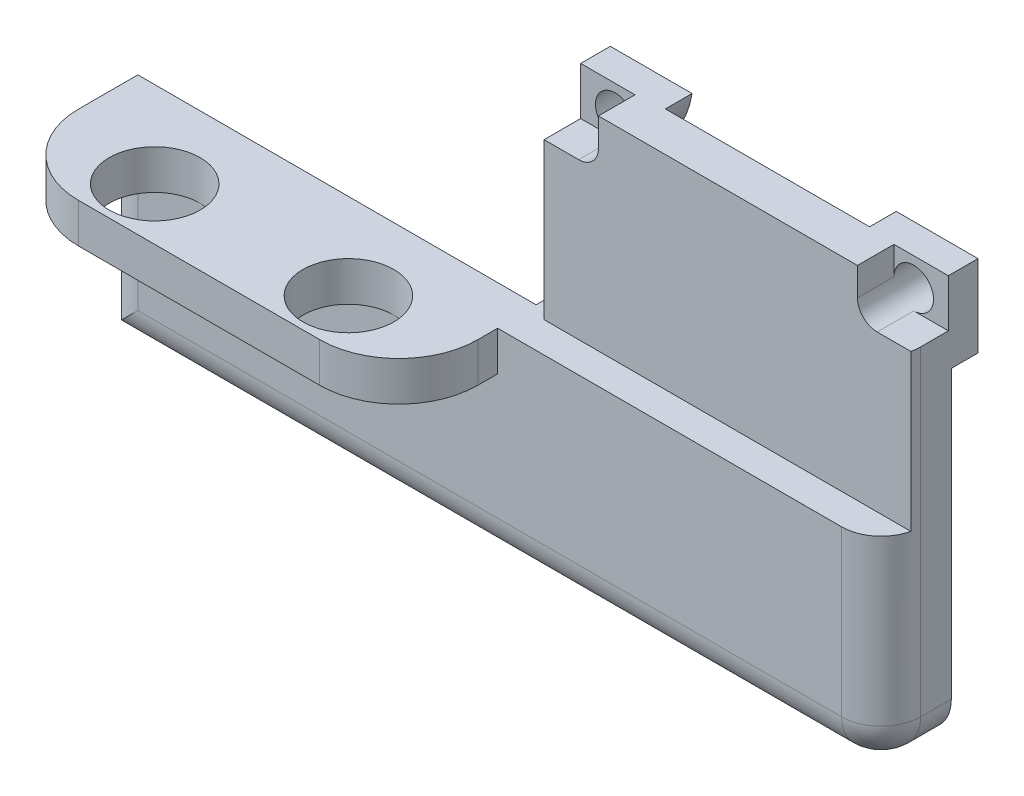
SolidWorks part; units mm, degrees
ref_plane "前视基准面" through (0, 0, 0) normal (0, 0, 1) x (1, 0, 0)
ref_plane "上视基准面" through (0, 0, 0) normal (0, 1, 0) x (1, 0, 0)
ref_plane "右视基准面" through (0, 0, 0) normal (1, 0, 0) x (0, 0, -1)
sketch "草图1" plane through (0, 0, 0) normal (0, 0, 1) x (1, 0, 0)
  line L0 (-10.1, 10.325) -> (10.1, 10.325)
  line L1 (-10.1, 20.65) -> (-10.1, 0) construction
  line L2 (10.1, 20.65) -> (10.1, 0) construction
  line L3 (10.1, 10.325) -> (10.1, 20.65)
  line L4 (10.1, 20.65) -> (-10.1, 20.65)
  line L5 (-10.1, 20.65) -> (-10.1, 10.325)
extrude "凸台-拉伸1" add sketch "草图1" along normal blind 2
ref_plane "基准面1" through (2.6077, 20.65, -27.85) normal (1, 0, 0) x (0, 0, -1)
sketch "草图3" plane through (0, 0, 2) normal (0, 0, 1) x (1, 0, 0)
  line L0 (-10.1, 20.65) -> (-10.1, 18.65)
  line L1 (-10.1, 20.65) -> (-10.1, 10.325) construction
  line L2 (-10.1, 18.65) -> (10.1, 18.65)
  line L3 (10.1, 10.325) -> (10.1, 20.65) construction
  line L4 (10.1, 18.65) -> (10.1, 20.65)
  line L5 (10.1, 20.65) -> (-10.1, 20.65)
extrude "凸台-拉伸2" add sketch "草图3" along normal blind 5
sketch "草图4" plane through (0, 18.65, 0) normal (0, -1, 0) x (1, 0, 0)
  circle A0 centre (-4.9, 4.35) radius 2.3
  circle A1 centre (4.9, 4.35) radius 2.3
  arc A2 (-5.377, 6.6) -> (-4.423, 6.6) centre (-4.9, 4.35) ccw construction
  arc A3 (4.423, 6.6) -> (5.377, 6.6) centre (4.9, 4.35) ccw construction
extrude "切除-拉伸1" cut sketch "草图4" against normal blind 2
sketch "草图5" plane through (0, 0, -1.55) normal (0, 0, 1) x (1, 0, 0)
  line L1 (15.0356, 30.95) -> (10.9, 30.95)
  line L2 (10.9, 30.95) -> (10.9, 26.8144)
  line L3 (10.9, 26.8144) -> (10.9, 10.325)
  line L4 (10.9, 26.8144) -> (10.9, -4.0444) construction
  line L5 (10.9, 10.325) -> (29.5, 10.325)
  line L6 (29.5, -4.0444) -> (29.5, 26.8144) construction
  line L7 (29.5, 10.325) -> (29.5, 26.8144)
  line L9 (25.3644, 30.95) -> (29.5, 30.95)
  line L11 (15.0356, 30.95) -> (25.3644, 30.95)
  line L12 (29.5, 26.8144) -> (29.5, 30.95)
  line L13 (-10.1, 10.325) -> (10.1, 10.325) construction
  line L14 (10.9, 20.65) -> (29.5, 20.65)
  line L15 (10.1, 20.65) -> (-10.1, 20.65) construction
  line L16 (10.9, 20.65) -> (10.0451, 20.65)
  line L17 (10.9, 10.325) -> (10.0451, 10.325)
  line L18 (10.0451, 10.325) -> (10.0451, 20.65)
  arc M11 (29.5, 26.8144) -> (25.3644, 30.95) centre (30.3, 31.75) cw
  line M12 (25.3644, 30.95) -> (15.0356, 30.95)
  arc M13 (15.0356, 30.95) -> (10.9, 26.8144) centre (10.1, 31.75) cw
  line M14 (10.9, 26.8144) -> (10.9, -4.0444)
  line M18 (29.5, -4.0444) -> (29.5, 26.8144)
extrude "凸台-拉伸3" add sketch "草图5" along normal up to vertex (3.55 mm away) contours L18 L17 L3 L16 | L14 L3 L5 M18 region at (20.2, 15.4875, -1.55) region at (10.4726, 15.4875, -1.55) up to point (10.1, 10.325, 2)
extrude "凸台-拉伸5" add sketch "草图5<6>" along normal blind 2 contours L14 L7 M14 M11 M12 M13 region at (20.2, 25.287, -1.55)
sketch "草图5<6>" plane through (0, 0, -1.55) normal (0, 0, 1) x (1, 0, 0) same geometry as "草图5"
sketch "草图7" plane through (0, 0, -2.9) normal (0, 0, 1) x (1, 0, 0)
  line L0 (10.9, 30.95) -> (10.9, 26.8144) construction
  line L1 (10.9, 30.95) -> (10.9, 26.8144)
  line L2 (15.0356, 30.95) -> (10.9, 30.95) construction
  line L3 (15.0356, 30.95) -> (10.9, 30.95)
  arc A0 (10.9, 26.8144) -> (15.0356, 30.95) centre (10.1, 31.75) ccw construction
  circle A1 centre (12.65, 29.535) radius 1
  circle A2 centre (12.65, 29.535) radius 1
  arc A3 (10.9, 26.8144) -> (15.0356, 30.95) centre (10.1, 31.75) ccw
  dimension "D1" = 0
extrude "凸台-拉伸6" add sketch "草图7" along normal blind 1.5
sketch "草图8" plane through (0, 0, -1.4) normal (0, 0, 1) x (1, 0, 0)
  line L0 (13.65, 29.535) -> (13.65, 30.95)
  line L1 (15.0356, 30.95) -> (10.9, 30.95) construction
  line L3 (13.65, 30.95) -> (15.0356, 30.95)
  line L4 (10.9, 28.535) -> (10.9, 26.8144)
  line L5 (12.65, 28.535) -> (10.9, 28.535)
  line L6 (10.9, 30.95) -> (10.9, 26.8144) construction
  arc A0 (10.9, 26.8144) -> (15.0356, 30.95) centre (10.1, 31.75) ccw construction
  arc A1 (10.9, 26.8144) -> (15.0356, 30.95) centre (10.1, 31.75) ccw
  circle A2 centre (12.65, 29.535) radius 1 construction
  arc A4 (12.65, 28.535) -> (13.65, 29.535) centre (12.65, 29.535) ccw
extrude "凸台-拉伸7" add sketch "草图8" along normal up to vertex up to point (15.0356, 30.95, 0.45)
sketch "草图9" plane through (0, 0, -2.9) normal (0, 0, 1) x (1, 0, 0)
  line L0 (26.75, 29.535) -> (26.75, 30.95)
  line L1 (29.5, 30.95) -> (25.3644, 30.95) construction
  line L2 (26.75, 30.95) -> (25.3644, 30.95)
  line L3 (27.75, 28.535) -> (29.5, 28.535)
  line L4 (26.75, 30.95) -> (29.5, 30.95)
  line L5 (29.5, 26.8144) -> (29.5, 30.95) construction
  line L6 (29.5, 30.95) -> (29.5, 28.535)
  line L7 (29.5, 28.535) -> (29.5, 26.8144)
  circle A0 centre (27.75, 29.535) radius 1 construction
  arc A2 (26.75, 29.535) -> (27.75, 28.535) centre (27.75, 29.535) ccw
  arc A3 (25.3644, 30.95) -> (29.5, 26.8144) centre (30.3, 31.75) ccw construction
  arc A4 (25.3644, 30.95) -> (29.5, 26.8144) centre (30.3, 31.75) ccw
  circle M6 centre (27.75, 29.535) radius 1
  line M7 (29.5, 26.8144) -> (29.5, 30.95)
  line M8 (29.5, 30.95) -> (25.3644, 30.95)
  arc M9 (25.3644, 30.95) -> (29.5, 26.8144) centre (30.3, 31.75) ccw
extrude "凸台-拉伸8" add sketch "草图9" along normal blind 2 contours L3 L0 M6 M8 M9 M7 region at (27.0015, 28.7865, -2.9)
sketch "草图11" plane through (0, 0, -0.9) normal (0, 0, 1) x (1, 0, 0)
  line L4 (29.5, 28.535) -> (27.75, 28.535)
  line L5 (26.75, 29.535) -> (26.75, 30.95)
  line L6 (26.75, 30.95) -> (25.3644, 30.95)
  line L7 (29.5, 26.8144) -> (29.5, 28.535)
  line L8 (29.5, 28.535) -> (27.75, 28.535)
  line L9 (26.75, 29.535) -> (26.75, 30.95)
  line L10 (26.75, 30.95) -> (25.3644, 30.95)
  line L11 (29.5, 26.8144) -> (29.5, 28.535)
  arc A2 (26.75, 29.535) -> (27.75, 28.535) centre (27.75, 29.535) ccw
  arc A3 (25.3644, 30.95) -> (29.5, 26.8144) centre (30.3, 31.75) ccw
  arc A4 (26.75, 29.535) -> (27.75, 28.535) centre (27.75, 29.535) ccw
  arc A5 (25.3644, 30.95) -> (29.5, 26.8144) centre (30.3, 31.75) ccw
  dimension "D1" = 0
extrude "凸台-拉伸9" add sketch "草图11" along normal up to vertex up to point (25.3644, 30.95, 0.45)
ref_plane "基准面2" through (29.2, 30.55, -30.65) normal (-1, 0, 0) x (0, 0, 1)
sketch "草图13" plane through (0, 0, -2.9) normal (0, 0, 1) x (1, 0, 0)
  line L0 (26.75, 30.95) -> (26.75, 29.535)
  line L1 (27.75, 28.535) -> (29.5, 28.535)
  line L2 (29.5, 30.95) -> (29.5, 28.535)
  line L3 (29.5, 30.95) -> (26.75, 30.95)
  line L8 (29.5, 26.8144) -> (29.5, 30.95)
  line L9 (29.5, 30.95) -> (25.3644, 30.95)
  line L10 (29.5, 28.535) -> (29.5, 30.95)
  line L11 (29.5, 30.95) -> (26.75, 30.95)
  circle A0 centre (27.75, 29.535) radius 1 construction
  arc A1 (25.3644, 30.95) -> (29.5, 26.8144) centre (30.3, 31.75) ccw
  arc A4 (27.75, 28.535) -> (26.75, 29.535) centre (27.75, 29.535) ccw
  circle M8 centre (27.75, 29.535) radius 1
  line M9 (29.5, 26.8144) -> (29.5, 30.95)
  line M10 (29.5, 30.95) -> (25.3644, 30.95)
  dimension "D1" = 0
extrude "凸台-拉伸10" add sketch "草图13" along normal blind 1.5 contours L1 L0 M8 M9 M10 region at (28.125, 30.9134, -2.9)
fillet "圆角1" radius 2 4 edges at (29.5, 10.325, 0.225) (-10.1, 14.4875, 2) (29.5, 15.4875, 2) (9.7, 10.325, 2)
fillet "圆角2" radius 4 1 edges at (-10.1, 19.65, 7) type face fillet first side face at (-10.1, 19.65, 3.5) second side face at (0, 19.65, 7)
fillet "圆角3" radius 4 1 edges at (10.1, 19.65, 7) type face fillet first side face at (10.1, 19.65, 4.5) second side face at (2, 19.65, 7)
